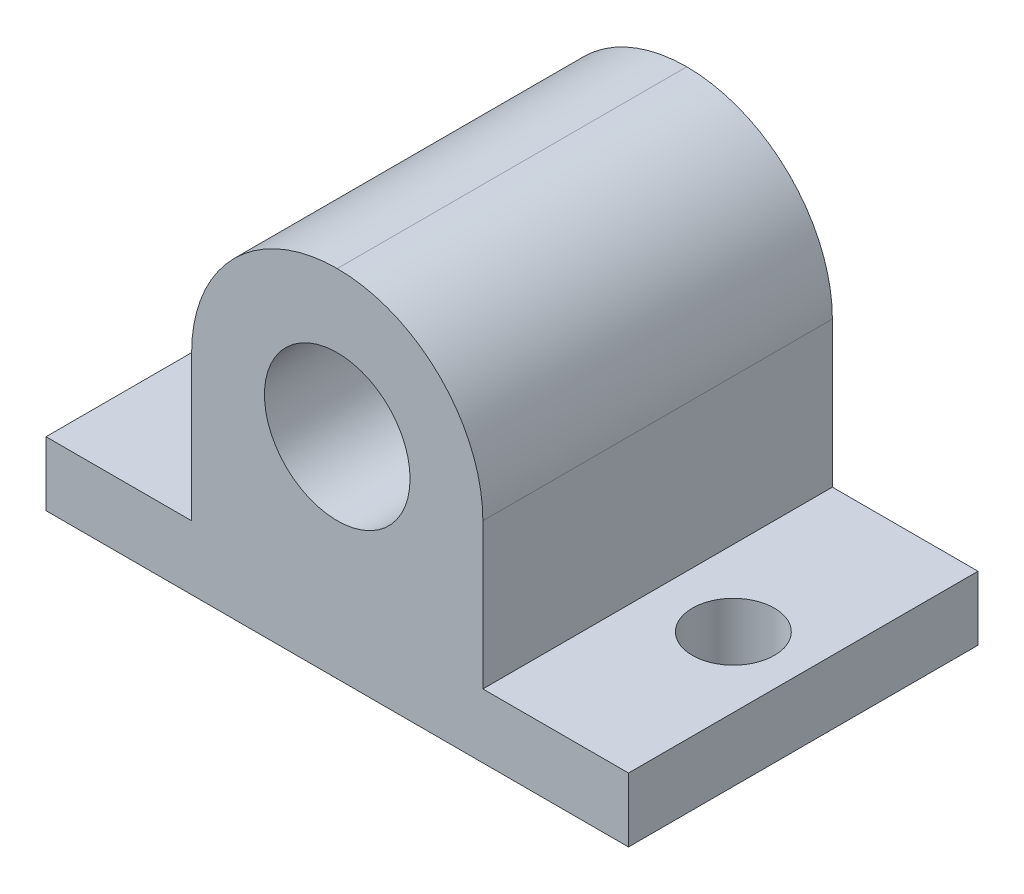
SolidWorks part; units mm, degrees
ref_plane "Front Plane" through (0, 0, 0) normal (0, 0, 1) x (1, 0, 0)
ref_plane "Top Plane" through (0, 0, 0) normal (0, 1, 0) x (1, 0, 0)
ref_plane "Right Plane" through (0, 0, 0) normal (1, 0, 0) x (0, 0, -1)
sketch "Sketch1" plane through (0, 0, 0) normal (0, 1, 0) x (1, 0, 0)
  line L1 (0, 0) -> (25.4, 0)
  line L2 (0, 0) -> (0, 15.24)
  line L3 (0, 15.24) -> (25.4, 15.24)
  line L4 (25.4, 0) -> (25.4, 15.24)
  dimension "D1" = 25.4
  dimension "D2" = 15.24
extrude "Boss-Extrude1" add sketch "Sketch1" along normal blind 2.794
sketch "Sketch2" plane through (0, 2.794, 0) normal (0, 1, 0) x (1, 0, 0)
  line L0 (25.4, 15.24) -> (0, 15.24) construction
  line L1 (6.35, 15.24) -> (19.05, 15.24)
  line L2 (6.35, 15.24) -> (6.35, 0)
  line L3 (6.35, 0) -> (19.05, 0)
  line L4 (19.05, 15.24) -> (19.05, 0)
  line L5 (0, 0) -> (25.4, 0) construction
  line L6 (0, 15.24) -> (6.35, 15.24) construction
  line L7 (19.05, 15.24) -> (25.4, 15.24) construction
  dimension "D1" = 12.7
extrude "Boss-Extrude2" add sketch "Sketch2" along normal blind 12.7
fillet "Fillet1" radius 6.35 2 edges at (6.35, 15.494, -7.62) (19.05, 15.494, -7.62)
sketch "Sketch3" plane through (0, 0, 0) normal (0, 0, 1) x (1, 0, 0)
  circle A0 centre (12.7, 9.144) radius 3.175
  dimension "D1" = 6.35
extrude "Cut-Extrude1" cut sketch "Sketch3" against normal through all
sketch "Sketch4" plane through (0, 2.794, 0) normal (0, 1, 0) x (1, 0, 0)
  line L0 (6.35, 15.24) -> (0, 15.24) construction
  line L3 (25.4, 15.24) -> (19.05, 15.24) construction
  line L5 (12.7, 0) -> (12.7, 15.24) construction
  circle A0 centre (3.048, 7.62) radius 1.7875
  circle A1 centre (22.352, 7.62) radius 1.7875
  dimension "D1" = 7.62
  dimension "D2" = 7.62
  dimension "D3" = 9.652
  dimension "D4" = 9.652
extrude "Cut-Extrude2" cut sketch "Sketch4" against normal through all
